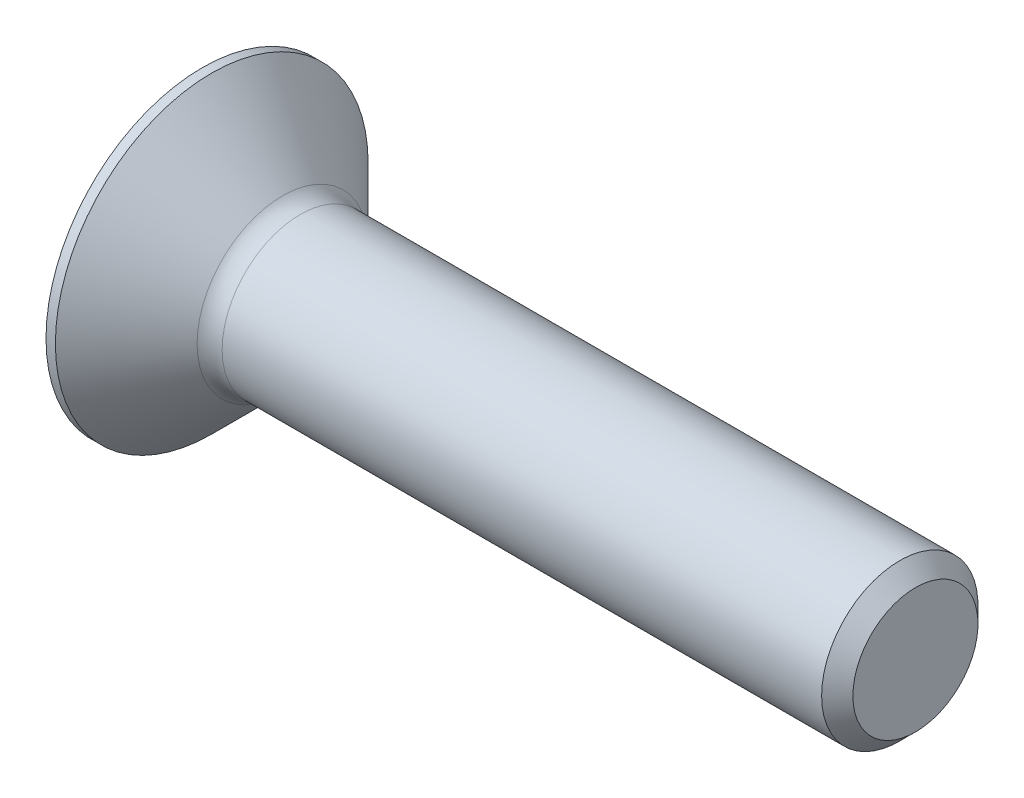
SolidWorks part; units mm, degrees
ref_plane "Plane1" through (0, 0, 0) normal (0, 0, 1) x (1, 0, 0)
ref_plane "Plane2" through (0, 0, 0) normal (0, 1, 0) x (1, 0, 0)
ref_plane "Plane3" through (0, 0, 0) normal (1, 0, 0) x (0, 0, -1)
sketch "BodySke" plane through (0, 0, 0) normal (0, 0, 1) x (1, 0, 0)
  line L0 (0, 0) -> (0, 5)
  line L1 (0.3, 5) -> (2.8, 2.5)
  line L2 (0, 5) -> (0.3, 5)
  line L3 (2.8, 2.5) -> (22.3, 2.5)
  line L4 (22.8, 2) -> (22.8, 0)
  line L5 (22.8, 0) -> (0, 0)
  line L6 (0, 0) -> (127, 0) construction
  line L7 (0.3, -5) -> (2.8, -2.5) construction
  line L8 (22.8, 2) -> (22.3, 2.5)
  line L9 (0, -5) -> (0.3, -5) construction
  line L10 (22.8, -2) -> (22.3, -2.5) construction
  line L11 (3.1198, 12.35) -> (3.1198, -9.875) construction
  line L12 (5, 19.05) -> (5, -3.175) construction
  dimension "D1" = 2.8
  dimension "D2" = 20
  dimension "Diameter" = 5
  dimension "Body_ch_ang" = 45
  dimension "Head_dia" = 10
  dimension "Minor_dia" = 4
  dimension "Head_ang" = 90
revolve "BaseBody" add sketch "BodySke" angle 360 about L6
cosmetic thread "ThreadCosmetic" parameters "Thread_minor"=4
fillet "Fillet1" radius 0.8 1 edges at (2.8, 0, 2.5)
sketch "Sketch2" plane through (0, 0, 0) normal (0, 0, 1) x (1, 0, 0)
  line L0 (0, 1.5) -> (3.5, 1.5)
  line L1 (3.5, 1.5) -> (4.366, 0)
  line L2 (0, 0) -> (127, 0) construction
  line L3 (4.366, 0) -> (0, 0)
  line L4 (0, 0) -> (0, 1.5)
  line L5 (0, -1.5) -> (3.5, -1.5) construction
  line L6 (0, 0) -> (47.625, 0) construction
  line L8 (0, 5) -> (0, -5) construction
  dimension "D2" = 60
  dimension "PreBroach_depth" = 3.5
  dimension "PreBroach_dia" = 3
revolve "PreBroach" cut sketch "Sketch2" angle 360 about L6
sketch "Sketch3" plane through (0, 0, 0) normal (-1, 0, 0) x (0, 0, 1)
  line L0 (-1.5, -0.866) -> (-1.5, 0.866)
  line L1 (-1.5, 0.866) -> (0, 1.7321)
  line L2 (0, 1.7321) -> (1.5, 0.866)
  line L3 (1.5, 0.866) -> (1.5, -0.866)
  line L4 (1.5, -0.866) -> (0, -1.7321)
  line L5 (0, -1.7321) -> (-1.5, -0.866)
  dimension "D1" = 1.5
  dimension "D2" = 1.5
  dimension "D3" = 3
  dimension "Hex_size" = 3
extrude "Hex" cut sketch "Sketch3" against normal blind 5.6
sketch "ThdSchSke" plane through (0, 0, 0) normal (0, 0, 1) x (1, 0, 0)
  line L0 (17.66, -2) -> (17.3099, -2.5)
  line L1 (17.66, -2) -> (18.0101, -2.5)
  line L2 (18.0101, -2.5) -> (18.0101, -3.125)
  line L3 (-3.175, 0) -> (5.1513, 0) construction
  line L4 (0, 5) -> (0, -5) construction
  line L5 (18.0101, -3.125) -> (17.3099, -3.125)
  line L6 (17.3099, -3.125) -> (17.3099, -2.5)
  dimension "Thread_minor" = 4
  dimension "Diameter" = 5
  dimension "Start" = 17.66
  dimension "SideAngle" = 55
  dimension "VeeAngle" = 70
  dimension "Overcut" = 6.25
revolve "ThreadSchematic" [suppressed] cut sketch "ThdSchSke" angle 360 about L3
pattern_linear "ThdSchPat" [suppressed]
equation "\"Thread_minor@ThreadCosmetic\"  =  \"Minor_dia@BodySke\""
equation "\"D1@Sketch3\" = \"Hex_size@Sketch3\" / 2"
equation "\"D2@Sketch3\" = \"D1@Sketch3\""
equation "\"D3@Sketch3\" = \"Hex_size@Sketch3\""
equation "\"Thread_length@ThreadCosmetic\" = ((sgn( (\"Length@BodySke\" - \"Advance@BodySke\" * 3.0 - \"Head_ht@BodySke\" ) - \"Thread_nom@BodySke\" )-1)*( (\"Length@BodySke\" - \"Advance@BodySke\" * 3.0 - \"Head_ht@BodySke\" ) - \"Thread_nom@BodySke\" ))/-2+ \"Thread_nom@BodySke\""
equation "\"Thread_minor@ThdSchSke\" = \"Minor_dia@BodySke\""
equation "\"Diameter@ThdSchSke\" = \"Diameter@BodySke\""
equation "\"Overcut@ThdSchSke\" = \"Diameter@BodySke\" * 1.25"
equation "\"Num_threads@ThdSchPat\" = int( \"Thread_length@ThreadCosmetic\" / \"Advance@BodySke\" + 0.999 )  + 1"
equation "\"Num_threads@ThdSchPat\" = \"Num_threads@ThdSchPat\" - sgn( \"Num_threads@ThdSchPat\" - 1) '---chamfered tips only---"
